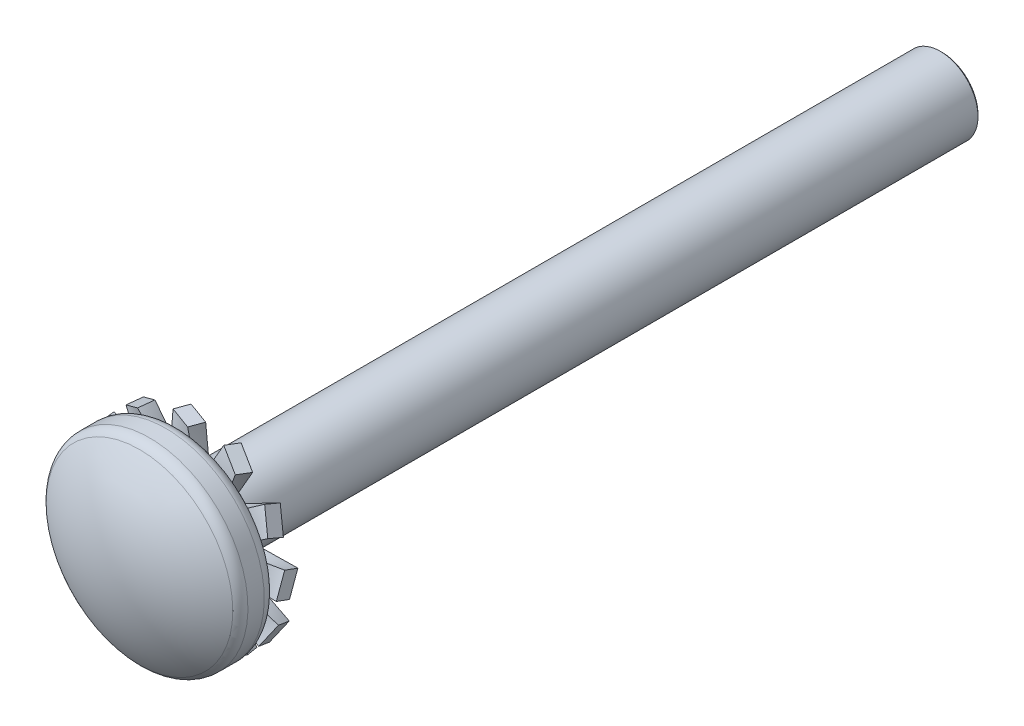
SolidWorks part; units mm, degrees
material "AISI 304"
ref_plane "Front Plane" through (0, 0, 0) normal (0, 0, 1) x (1, 0, 0)
ref_plane "Top Plane" through (0, 0, 0) normal (0, 1, 0) x (1, 0, 0)
ref_plane "Right Plane" through (0, 0, 0) normal (1, 0, 0) x (0, 0, -1)
sketch "Sketch1" plane through (0, 0, 0) normal (0, 0, 1) x (1, 0, 0)
  circle A0 centre (0, 0) radius 2.0828
  dimension "decimal equ" = 4.1656
curve "Helix/Spiral1" pitch 0.7937 height 32.5437 turns 41 parameters "helix length"=32.5437, "pitch"=0.7937
sketch "Sketch2" plane through (0, 0, 0) normal (1, 0, 0) x (0, 0, -1)
  line L0 (0.2977, 2.0828) -> (0.3969, 2.0828)
  line L1 (0.3969, 2.0828) -> (0.6945, 1.5672)
  line L2 (0.2977, 2.0828) -> (0, 1.5672)
  line L3 (0, 1.5672) -> (0.6945, 1.5672)
  line L4 (0.3473, 2.0828) -> (0.3473, 1.5672) construction
  line L6 (0.1488, 1.825) -> (0.5457, 1.825) construction
  line L7 (0, 1.5672) -> (0, 2.0828) construction
  line L8 (0, 2.0828) -> (0, -2.0828) construction
  line L9 (0, 2.0828) -> (0, -2.0828) construction
  point P8 (-3.2742, -2.0828)
  dimension "D1" = 60
  dimension "D3" = 0.0992
  dimension "D4" = 0.3969
  dimension "D2" = 3.2742
sketch "Sketch3" plane through (0, 0, 0) normal (1, 0, 0) x (0, 0, -1)
  line L0 (0, 0) -> (-31.75, 0) construction
  line L1 (0, 1.5672) -> (0.6945, 1.5672) construction
  line L2 (0, 0) -> (-31.75, 0)
  line L3 (0, 0) -> (0, 1.5672)
  line L4 (0, 1.5672) -> (-31.75, 1.5672)
  line L5 (-31.75, 0) -> (-31.75, 1.5672)
  dimension "length" = 31.75
revolve "Revolve1" add sketch "Sketch3" angle 360 about L0
sweep "Sweep1" [suppressed] add profiles "Sketch2" path "Helix/Spiral1"
sketch "Sketch39" plane through (0, 0, 0) normal (0, 0, -1) x (-1, 0, 0)
  circle A0 centre (0, 0) radius 2.0828 construction
  circle A1 centre (0, 0) radius 2.0828
extrude "Extrude5" [suppressed] cut sketch "Sketch39" along normal through all
sketch "Sketch38" plane through (0, 0, 0) normal (0, 0, -1) x (-1, 0, 0)
  circle A2 centre (0, 0) radius 1.4875
  circle A3 centre (0, 0) radius 1.4875
extrude "Extrude6" cut sketch "Sketch38" against normal through all draft 45 flip side to cut
sketch "Sketch10" plane through (0, 0, 0) normal (1, 0, 0) x (0, 0, -1)
  line L0 (0, 0) -> (23.0169, 0) construction
  line L1 (-285.75, 12.7) -> (-31.75, 12.7)
  line L2 (-285.75, 12.7) -> (-285.75, 0)
  line L3 (-285.75, 0) -> (-31.75, 0)
  line L4 (-31.75, 12.7) -> (-31.75, 0)
  line L5 (-31.75, 0) -> (-31.75, 1.5672) construction
  dimension "D1" = 254
  dimension "D2" = 12.7
revolve "Cut-Revolve2" [suppressed] cut sketch "Sketch10" angle 360 about L0
sketch "Sketch41" plane through (0, 0, 0) normal (1, 0, 0) x (0, 0, -1)
  line L0 (-31.75, 2.0828) -> (-31.75, 1.5672)
  line L1 (-31.75, 1.5672) -> (-30.8737, 1.5672)
  line L2 (-30.8737, 1.5672) -> (-30.3581, 2.0828)
  line L3 (-31.75, 2.0828) -> (-30.3581, 2.0828)
  line L4 (0, 1.5672) -> (0.6945, 1.5672) construction
  dimension "D1" = 0.8763
  dimension "D2" = 45
revolve "Cut-Revolve4" [suppressed] cut sketch "Sketch41" angle 360 about L2
sketch "Sketch8" plane through (0, 0, 0) normal (1, 0, 0) x (0, 0, -1)
  line L0 (0, 0) -> (-6.2449, 0) construction
  line L1 (-34.671, 0) -> (-31.75, 0)
  line L2 (-34.671, 0) -> (-34.671, 4.0894)
  line L3 (-34.671, 4.0894) -> (-31.75, 4.0894)
  line L4 (-31.75, 0) -> (-31.75, 4.0894)
  line L5 (-34.671, -4.0894) -> (-31.75, -4.0894) construction
  line L6 (-31.75, 0) -> (-31.75, 1.5672) construction
  dimension "head dia" = 8.1788
  dimension "head height" = 2.921
revolve "Revolve2" add sketch "Sketch8" angle 360 about L0
sketch "Sketch11" plane through (0, 0, 0) normal (1, 0, 0) x (0, 0, -1)
  line L0 (-33.2105, 4.0894) -> (-33.2105, -4.0894) construction
  line L1 (-34.671, 0) -> (-6.8951, 0) construction
  line L2 (-34.671, 4.0894) -> (-31.75, 4.0894) construction
  line L3 (-34.671, 0) -> (-34.671, 4.0894) construction
  line L4 (-32.9549, 4.0894) -> (-32.2758, 4.0894)
  line L6 (-31.75, 0) -> (-31.75, 4.0894) construction
  line L7 (-31.75, 3.5636) -> (-31.115, 3.5636)
  line L8 (-31.115, 3.5636) -> (-31.115, 4.7244)
  line L9 (-31.115, 4.7244) -> (-35.306, 4.7244)
  line L10 (-35.306, 4.7244) -> (-35.306, 0)
  line L11 (-35.306, 0) -> (-34.671, 0)
  arc A0 (-33.3751, 3.8796) -> (-34.671, 0) centre (-28.2156, 0) ccw
  arc A1 (-31.75, 3.5636) -> (-32.2758, 4.0894) centre (-32.2758, 3.5636) ccw
  arc A2 (-33.3751, 3.8796) -> (-32.9549, 4.0894) centre (-32.9549, 3.5636) cw
  dimension "D1" = 0.5258
  dimension "D2" = 0.635
  dimension "D3" = 0.635
  dimension "D4" = 0.635
revolve "Cut-Revolve3" cut sketch "Sketch11" angle 360 about L1
ref_plane "Plane1" through (0, 0, 34.671) normal (0, 0, 1) x (1, 0, 0)
sketch "Sketch12" plane through (0, 0, 34.671) normal (0, 0, 1) x (1, 0, 0)
  line L0 (0.508, 2.3264) -> (0.508, 1.1906)
  line L1 (0.508, 1.1906) -> (1.1906, 0.508) construction
  line L2 (1.1906, 0.508) -> (2.3264, 0.508)
  line L3 (0, 2.3813) -> (0, 0)
  line L4 (0, 0) -> (2.3813, 0)
  line L5 (0, 0) -> (0, 4.0894) construction
  line L6 (0, 0) -> (0.8493, 0.8493) construction
  line L7 (1.1906, 0) -> (1.1906, 1.5633) construction
  line L8 (0.508, 1.1906) -> (0.7079, 0.7079)
  line L9 (1.1906, 0.508) -> (0.7079, 0.7079)
  line L10 (0, 0) -> (0, -1.0114) construction
  line L11 (-0.508, 2.3264) -> (-0.508, 1.1906) construction
  arc A0 (2.3813, 0) -> (2.3264, 0.508) centre (0, 0) ccw
  arc A1 (0.508, 2.3264) -> (0, 2.3813) centre (0, 0) ccw
  arc A2 (-2.3813, 0) -> (-2.3264, 0.508) centre (0, 0) cw construction
  dimension "phillips dia" = 4.7625
  dimension "D2" = 45
  dimension "D4" = 22.5
  dimension "slot width" = 1.016
extrude "Cut-Extrude1" [suppressed] cut sketch "Sketch12" against normal blind 2.4829
draft "Draft3" [suppressed] type of draft neutral plane draft angle 15 neutral plane "Plane1" faces to draft 2 parameters "D1"=15
draft "Draft4" [suppressed] type of draft neutral plane draft angle 5 neutral plane "Plane1" faces to draft 4 parameters "D1"=5
pattern_circular "CirPattern1" [suppressed] count 4 over 360 about axis through (0, 0, 34.671) along (0, 0, -1) of bodies 110
ref_plane "Plane8" through (0, 0, 31.5939) normal (0, 0, -1) x (-1, 0, 0)
sketch "Sketch18" plane through (0, 0, 31.5939) normal (0, 0, 1) x (1, 0, 0)
  line L0 (0, 0) -> (0, 4.064) construction
  line L1 (1.5672, 0) -> (4.064, 0) construction
  circle A0 centre (0, 0) radius 4.064
  circle A1 centre (0, 0) radius 1.5672 construction
  circle A2 centre (0, 0) radius 1.5672 construction
  circle A3 centre (0, 0) radius 2.6908
  circle A4 centre (0, 0) radius 2.0828 construction
  point P8 (2.6908, 0)
  point P10 (0, 2.6908)
  dimension "washer dia." = 8.128
  dimension "D2" = 1.1235
sketch "Sketch21" plane through (0, 0, 31.5939) normal (0, 0, 1) x (1, 0, 0)
  circle A0 centre (0, 0) radius 2.6908
  circle A1 centre (0, 0) radius 1.5672
  circle A2 centre (0, 0) radius 2.0828 construction
extrude "Extrude2" add sketch "Sketch21" against normal blind 0.5842 separate body
ref_plane "Plane9" through (0, 2.6908, 0) normal (0, 1, 0) x (-1, 0, 0)
sketch "Sketch31" plane through (0, 2.6908, 0) normal (0, 1, 0) x (-1, 0, 0)
  line L1 (-0.508, 31.5939) -> (0.508, 31.5939)
  line L2 (-0.508, 31.5939) -> (-0.508, 31.0097)
  line L3 (-0.508, 31.0097) -> (0.508, 31.0097)
  line L4 (0.508, 31.5939) -> (0.508, 31.0097)
  line L5 (-2.6908, 31.0097) -> (2.6908, 31.0097) construction
  line L6 (0, 0) -> (0, 31.5939) construction
  line L7 (0.508, 31.3018) -> (-0.508, 31.3018) construction
  line L8 (0, 31.5939) -> (0, 31.0097) construction
  line L9 (2.6908, 31.5939) -> (-2.6908, 31.5939) construction
  dimension "D1" = 1.016
ref_plane "Plane10" through (0, 4.064, 0) normal (0, 1, 0) x (-1, 0, 0)
sketch "Sketch32" plane through (0, 4.064, 0) normal (0, 1, 0) x (-1, 0, 0)
  line L0 (-0.3775, 31.75) -> (-0.5773, 31.201)
  line L1 (-0.3775, 31.75) -> (0.5773, 31.4025)
  line L2 (-0.5773, 31.201) -> (0.3775, 30.8535)
  line L3 (0.5773, 31.4025) -> (0.3775, 30.8535)
  line L4 (-0.508, 31.5939) -> (-0.508, 31.0097) construction
  line L5 (-0.508, 31.0097) -> (0.508, 31.0097) construction
  line L6 (0.0999, 31.5763) -> (0, 31.3018) construction
  line L7 (0, 31.3018) -> (0.4774, 31.128) construction
  line L8 (0.508, 31.3018) -> (-0.508, 31.3018) construction
  line L9 (0, 0) -> (0, 6.2449) construction
  line L10 (-1.5672, 31.0097) -> (1.5672, 31.0097) construction
  dimension "D1" = 20
sketch "Sketch33" plane through (0, 2.6908, 0) normal (0, 1, 0) x (-1, 0, 0)
  line L1 (1.5672, 31.5939) -> (-1.5672, 31.5939) construction
  line L4 (0.508, 31.5939) -> (-0.508, 31.5939)
  line L5 (0.508, 31.0097) -> (0.508, 31.5939)
  line L6 (-0.508, 31.0097) -> (0.508, 31.0097)
  line L7 (-0.508, 31.5939) -> (-0.508, 31.0097)
  line L8 (0.508, 31.5939) -> (-0.508, 31.5939)
  line L9 (0.508, 31.0097) -> (0.508, 31.5939)
  line L10 (-0.508, 31.0097) -> (0.508, 31.0097)
  line L11 (-0.508, 31.5939) -> (-0.508, 31.0097)
  dimension "D1" = 0
extrude "Extrude3" add sketch "Sketch33" against normal up to next (1.1235 mm away)
loft "Loft2" add profiles "Sketch32", "Sketch31" connector at (0.3775, 4.064, 31.75) connector at (0.508, 2.6908, 31.5939)
pattern_circular "CirPattern4" count 12 over 360 about axis through (0, 0, 31.0097) along (0, 0, 1) of "Loft2", "Extrude3"
sketch "Sketch40" plane through (0, 0, 0) normal (1, 0, 0) x (0, 0, -1)
  line L0 (-31.5939, 4.064) -> (-31.0097, 4.064) construction
  line L1 (-31.5939, -4.064) -> (-31.0097, -4.064) construction
  line L2 (-31.3018, 4.064) -> (-31.3018, -4.064) construction
  line L3 (-31.3018, 0) -> (0, 0) construction
  line L4 (0, -1.4875) -> (0, 1.4875) construction
  line L6 (-31.5939, -5.9931) -> (-31.5939, 5.9931) construction
  dimension "D1" = 0.5842
  dimension "D2" = 8.128
equation "\"D3@Sketch2\" = \"pitch@Helix/Spiral1\"*.125"
equation "\"D4@Sketch2\" = \"pitch@Helix/Spiral1\"*.5"
equation "\"D1@Sketch11\" = \"head height@Sketch8\"*.18"
equation "\"D1@Cut-Extrude1\" = \"head height@Sketch8\"*.85"
equation "\"D1@Sketch31\" = \"washer dia.@Sketch18\"*.125"
equation "\"helix length@Helix/Spiral1\" = \"length@Sketch3\" + \"pitch@Helix/Spiral1\""
equation "\"D1@Sketch38\" = \"pitch@Helix/Spiral1\"*.750"
equation "\"D1@Plane8\" = \"D2@Sketch32\""
equation "\"D2@Sketch18\" = \"D1@Sketch18\"*.45"
equation "\"D2@Sketch2\" = \"pitch@Helix/Spiral1\"*4.125"
equation "\"D1@Sketch40\" = \"washer width@Extrude2\""
equation "\"D2@Sketch40\" = \"washer dia.@Sketch18\""
equation "\"D1@Sketch41\" = \"washer width@Extrude2\"*1.50"
